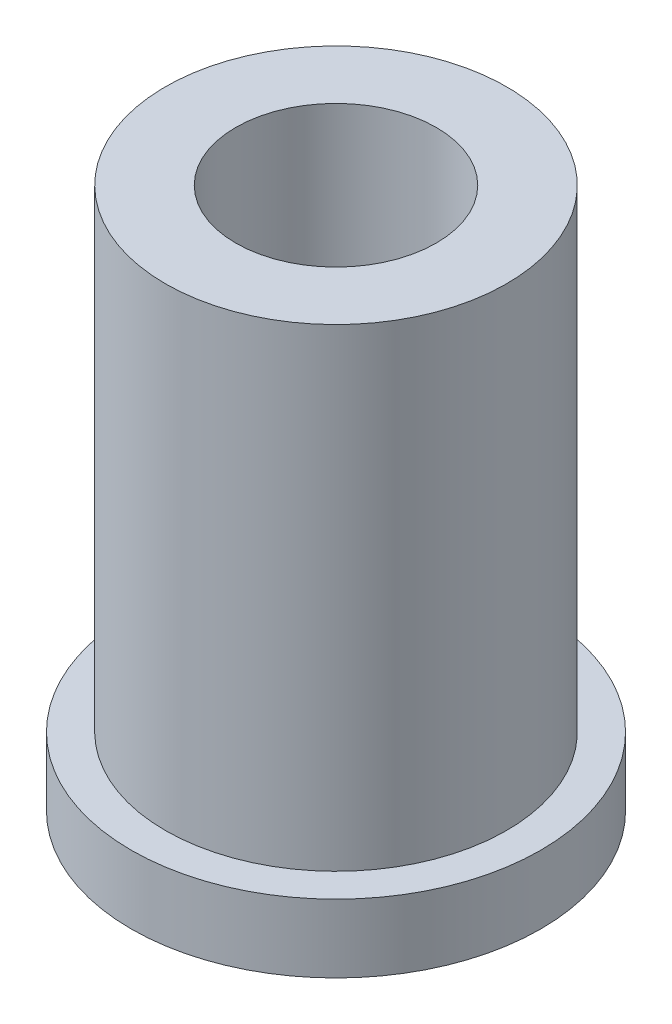
SolidWorks part; units mm, degrees
ref_plane "정면" through (0, 0, 0) normal (0, 0, 1) x (1, 0, 0)
ref_plane "윗면" through (0, 0, 0) normal (0, 1, 0) x (1, 0, 0)
ref_plane "우측면" through (0, 0, 0) normal (1, 0, 0) x (0, 0, -1)
sketch "스케치1" plane through (0, 0, 0) normal (0, 1, 0) x (1, 0, 0)
  circle A0 centre (0, 0) radius 4.8
  circle A1 centre (0, 0) radius 4
  circle A2 centre (0, 0) radius 2.35
  dimension "D1" = 9.6
  dimension "D2" = 8
  dimension "D3" = 4.7
extrude "보스-돌출1" add sketch "스케치1" along normal blind 12.7 contours A1 A2 region at (-3.8869, 0, 0)
extrude "보스-돌출2" add sketch "스케치1<3>" along normal blind 1.6 contours A0 A1 region at (-4.6642, 0, 0)
sketch "스케치1<3>" plane through (0, 0, 0) normal (0, 1, 0) x (1, 0, 0) same geometry as "스케치1"
